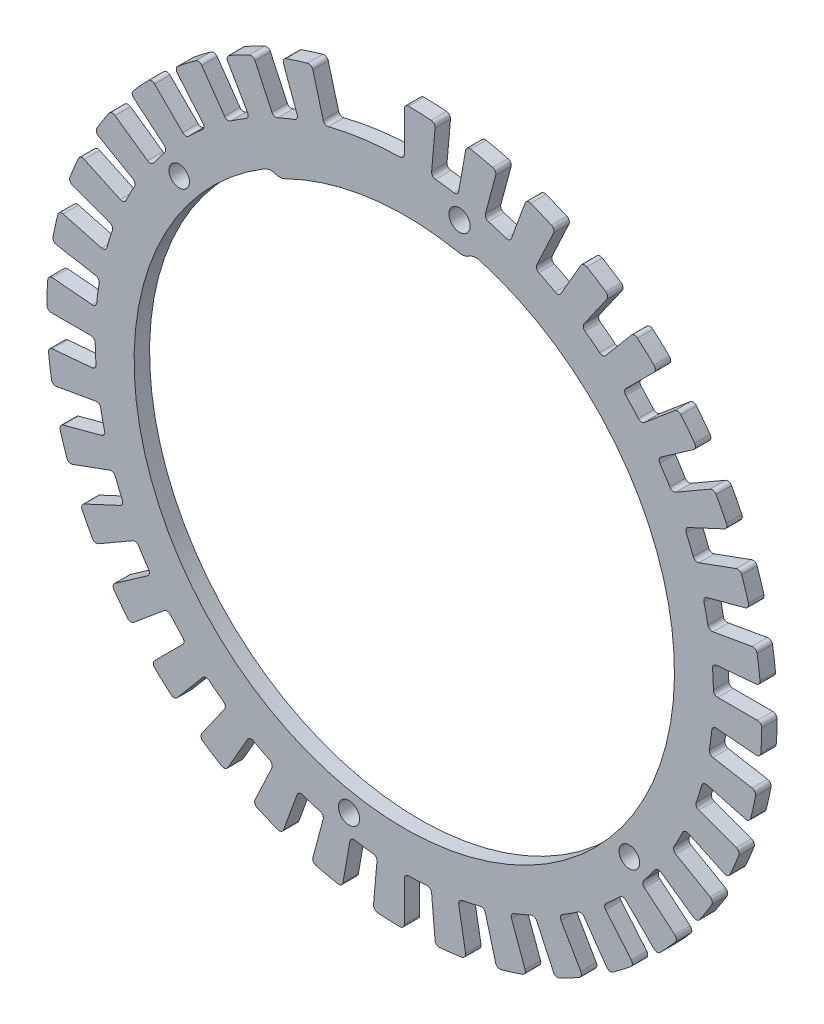
SolidWorks part; units mm, degrees
ref_plane "Front Plane" through (0, 0, 0) normal (0, 0, 1) x (1, 0, 0)
ref_plane "Top Plane" through (0, 0, 0) normal (0, 1, 0) x (1, 0, 0)
ref_plane "Right Plane" through (0, 0, 0) normal (1, 0, 0) x (0, 0, -1)
sketch "Sketch1" plane through (0, 0, 0) normal (0, 0, 1) x (1, 0, 0)
  line L0 (0, 82.7) -> (0, 71.5) construction
  line L1 (7.2078, 82.3853) -> (6.2316, 71.2279) construction
  line L2 (0, 71.5) -> (0, 0) construction
  line L3 (6.2316, 71.2279) -> (0, 0) construction
  line L4 (12.5883, 71.3918) -> (14.186, 80.4528) construction
  line L5 (12.5883, 71.3918) -> (0, 0) construction
  line L8 (0, 0) -> (12.7842, 65.769) construction
  line L12 (13.6428, 70.1863) -> (12.7842, 65.769) construction
  line L15 (12.7842, 65.769) -> (11.9256, 61.3517) construction
  line L18 (7.3144, 72.1301) -> (6.3182, 72.2172) construction
  line L21 (7.3144, 72.1301) -> (7.2135, 71.1352) construction
  line L24 (12.5883, 71.3918) -> (11.6035, 71.5654) construction
  line L27 (11.6035, 71.5654) -> (11.4434, 70.5783) construction
  line L30 (1.0122, 82.6938) -> (1, 81.6939) construction
  line L33 (1, 81.6939) -> (0, 81.6939) construction
  line L36 (7.1201, 81.383) -> (6.1239, 81.4702) construction
  line L39 (6.1239, 81.4702) -> (6.1989, 82.4674) construction
  line L42 (7.1201, 81.383) -> (6.3182, 72.2172)
  line L45 (0, 81.6939) -> (0, 72.4931)
  line L48 (0, 72.4931) -> (-1, 72.4931) construction
  line L51 (-1, 72.4931) -> (-0.9862, 71.4932) construction
  line L109 (0, -82.7) -> (0, -71.5) [skipped]
  line L111 (14.3607, 81.4436) -> (12.4158, 70.4138) [skipped]
  line L115 (41.35, 71.6203) -> (35.75, 61.9208) [skipped]
  line L117 (53.1585, 63.3519) -> (45.9593, 54.7722) [skipped]
  line L118 (-63.3519, -53.1585) -> (-54.7722, -45.9593) [skipped]
  line L119 (63.3519, 53.1585) -> (54.7722, 45.9593) [skipped]
  line L121 (71.6203, 41.35) -> (61.9208, 35.75) [skipped]
  line L123 (77.7126, 28.2851) -> (67.188, 24.4544) [skipped]
  line L125 (81.4436, 14.3607) -> (70.4138, 12.4158) [skipped]
  line L127 (82.7, 0) -> (71.5, 0) [skipped]
  line L129 (81.4436, -14.3607) -> (70.4138, -12.4158) [skipped]
  line L131 (77.7126, -28.2851) -> (67.188, -24.4544) [skipped]
  line L133 (71.6203, -41.35) -> (61.9208, -35.75) [skipped]
  line L135 (63.3519, -53.1585) -> (54.7722, -45.9593) [skipped]
  line L137 (53.1585, -63.3519) -> (45.9593, -54.7722) [skipped]
  line L139 (41.35, -71.6203) -> (35.75, -61.9208) [skipped]
  line L141 (28.2851, -77.7126) -> (24.4544, -67.188) [skipped]
  line L142 (14.3607, -81.4436) -> (12.4158, -70.4138) [skipped]
  line L143 (34.9505, 74.9517) -> (30.2172, 64.801) [skipped]
  line L144 (47.4348, 67.7439) -> (41.0107, 58.5694) [skipped]
  line L145 (58.4777, 58.4777) -> (50.5581, 50.5581) [skipped]
  line L146 (67.7439, 47.4348) -> (58.5694, 41.0107) [skipped]
  line L147 (74.9517, 34.9505) -> (64.801, 30.2172) [skipped]
  line L148 (79.8821, 21.4043) -> (69.0637, 18.5056) [skipped]
  line L149 (82.3853, 7.2078) -> (71.2279, 6.2316) [skipped]
  line L150 (82.3853, -7.2078) -> (71.2279, -6.2316) [skipped]
  line L151 (79.8821, -21.4043) -> (69.0637, -18.5056) [skipped]
  line L152 (74.9517, -34.9505) -> (64.801, -30.2172) [skipped]
  line L153 (67.7439, -47.4348) -> (58.5694, -41.0107) [skipped]
  line L154 (58.4777, -58.4777) -> (50.5581, -50.5581) [skipped]
  line L155 (47.4348, -67.7439) -> (41.0107, -58.5694) [skipped]
  line L156 (34.9505, -74.9517) -> (30.2172, -64.801) [skipped]
  line L157 (21.4043, -79.8821) -> (18.5056, -69.0637) [skipped]
  line L158 (7.2078, -82.3853) -> (6.2316, -71.2279) [skipped]
  line L159 (-7.2078, -82.3853) -> (-6.2316, -71.2279) [skipped]
  line L160 (-21.4043, -79.8821) -> (-18.5056, -69.0637) [skipped]
  line L161 (-34.9505, -74.9517) -> (-30.2172, -64.801) [skipped]
  line L162 (-47.4348, -67.7439) -> (-41.0107, -58.5694) [skipped]
  line L163 (-58.4777, -58.4777) -> (-50.5581, -50.5581) [skipped]
  line L164 (-67.7439, -47.4348) -> (-58.5694, -41.0107) [skipped]
  line L165 (-74.9517, -34.9505) -> (-64.801, -30.2172) [skipped]
  line L166 (-79.8821, -21.4043) -> (-69.0637, -18.5056) [skipped]
  line L167 (-82.3853, -7.2078) -> (-71.2279, -6.2316) [skipped]
  line L168 (-82.3853, 7.2078) -> (-71.2279, 6.2316) [skipped]
  line L169 (-79.8821, 21.4043) -> (-69.0637, 18.5056) [skipped]
  line L170 (-74.9517, 34.9505) -> (-64.801, 30.2172) [skipped]
  line L171 (-67.7439, 47.4348) -> (-58.5694, 41.0107) [skipped]
  line L172 (-58.4777, 58.4777) -> (-50.5581, 50.5581) [skipped]
  line L173 (-47.4348, 67.7439) -> (-41.0107, 58.5694) [skipped]
  line L174 (-34.9505, 74.9517) -> (-30.2172, 64.801) [skipped]
  line L175 (-21.4043, 79.8821) -> (-18.5056, 69.0637) [skipped]
  line L176 (21.4043, 79.8821) -> (18.5056, 69.0637) [skipped]
  line L209 (0, 0) -> (-12.7842, -65.769) construction
  line L210 (0, 0) -> (-52.0688, 42.1645) construction
  line L211 (0, 0) -> (52.0688, -42.1645) construction
  line L212 (14.186, 80.4528) -> (12.5883, 71.3918)
  line L213 (21.1439, 78.9102) -> (18.7626, 70.023)
  line L214 (27.941, 76.7671) -> (24.7941, 68.1212)
  line L215 (34.5253, 74.0398) -> (30.6369, 65.7011)
  line L216 (40.8469, 70.749) -> (36.2466, 62.7809)
  line L217 (46.8577, 66.9197) -> (41.5803, 59.3829)
  line L218 (52.5118, 62.5811) -> (46.5977, 55.5329)
  line L219 (57.7663, 57.7663) -> (51.2604, 51.2604)
  line L220 (62.5811, 52.5118) -> (55.5329, 46.5977)
  line L221 (66.9197, 46.8577) -> (59.3829, 41.5803)
  line L222 (70.749, 40.8469) -> (62.7809, 36.2466)
  line L223 (74.0398, 34.5253) -> (65.7011, 30.6369)
  line L224 (76.7671, 27.941) -> (68.1212, 24.7941)
  line L225 (78.9102, 21.1439) -> (70.023, 18.7626)
  line L226 (80.4528, 14.186) -> (71.3918, 12.5883)
  line L227 (81.383, 7.1201) -> (72.2172, 6.3182)
  line L228 (81.6939, 0) -> (72.4931, 0)
  line L229 (81.383, -7.1201) -> (72.2172, -6.3182)
  line L230 (80.4528, -14.186) -> (71.3918, -12.5883)
  line L231 (78.9102, -21.1439) -> (70.023, -18.7626)
  line L232 (76.7671, -27.941) -> (68.1212, -24.7941)
  line L233 (74.0398, -34.5253) -> (65.7011, -30.6369)
  line L234 (70.749, -40.8469) -> (62.7809, -36.2466)
  line L235 (66.9197, -46.8577) -> (59.3829, -41.5803)
  line L236 (62.5811, -52.5118) -> (55.5329, -46.5977)
  line L237 (57.7663, -57.7663) -> (51.2604, -51.2604)
  line L238 (52.5118, -62.5811) -> (46.5977, -55.5329)
  line L239 (46.8577, -66.9197) -> (41.5803, -59.3829)
  line L240 (40.8469, -70.749) -> (36.2466, -62.7809)
  line L241 (34.5253, -74.0398) -> (30.6369, -65.7011)
  line L242 (27.941, -76.7671) -> (24.7941, -68.1212)
  line L243 (21.1439, -78.9102) -> (18.7626, -70.023)
  line L244 (14.186, -80.4528) -> (12.5883, -71.3918)
  line L245 (7.1201, -81.383) -> (6.3182, -72.2172)
  line L246 (0, -81.6939) -> (0, -72.4931)
  line L247 (-7.1201, -81.383) -> (-6.3182, -72.2172)
  line L248 (-14.186, -80.4528) -> (-12.5883, -71.3918)
  line L249 (-21.1439, -78.9102) -> (-18.7626, -70.023)
  line L250 (-27.941, -76.7671) -> (-24.7941, -68.1212)
  line L251 (-34.5253, -74.0398) -> (-30.6369, -65.7011)
  line L252 (-40.8469, -70.749) -> (-36.2466, -62.7809)
  line L253 (-46.8577, -66.9197) -> (-41.5803, -59.3829)
  line L254 (-52.5118, -62.5811) -> (-46.5977, -55.5329)
  line L255 (-57.7663, -57.7663) -> (-51.2604, -51.2604)
  line L256 (-62.5811, -52.5118) -> (-55.5329, -46.5977)
  line L257 (-66.9197, -46.8577) -> (-59.3829, -41.5803)
  line L258 (-70.749, -40.8469) -> (-62.7809, -36.2466)
  line L259 (-74.0398, -34.5253) -> (-65.7011, -30.6369)
  line L260 (-76.7671, -27.941) -> (-68.1212, -24.7941)
  line L261 (-78.9102, -21.1439) -> (-70.023, -18.7626)
  line L262 (-80.4528, -14.186) -> (-71.3918, -12.5883)
  line L263 (-81.383, -7.1201) -> (-72.2172, -6.3182)
  line L264 (-81.6939, 0) -> (-72.4931, 0)
  line L265 (-81.383, 7.1201) -> (-72.2172, 6.3182)
  line L266 (-80.4528, 14.186) -> (-71.3918, 12.5883)
  line L267 (-78.9102, 21.1439) -> (-70.023, 18.7626)
  line L268 (-76.7671, 27.941) -> (-68.1212, 24.7941)
  line L269 (-74.0398, 34.5253) -> (-65.7011, 30.6369)
  line L270 (-70.749, 40.8469) -> (-62.7809, 36.2466)
  line L271 (-66.9197, 46.8577) -> (-59.3829, 41.5803)
  line L272 (-62.5811, 52.5118) -> (-55.5329, 46.5977)
  line L273 (-57.7663, 57.7663) -> (-51.2604, 51.2604)
  line L274 (-52.5118, 62.5811) -> (-46.5977, 55.5329)
  line L275 (-46.8577, 66.9197) -> (-41.5803, 59.3829)
  line L276 (-40.8469, 70.749) -> (-36.2466, 62.7809)
  line L277 (-34.5253, 74.0398) -> (-30.6369, 65.7011)
  line L278 (-27.941, 76.7671) -> (-24.7941, 68.1212)
  line L279 (-21.1439, 78.9102) -> (-18.7626, 70.023)
  line L280 (-0.9864, 71.4932) -> (-0.9862, 71.4932)
  line L281 (-32.3995, 53.4464) -> (-30.8444, 50.881) construction
  line L282 (-30.8444, 50.881) -> (-29.8635, 53.7161) construction
  line L283 (-29.8635, 53.7161) -> (-28.8826, 56.5512) construction
  line L284 (-28.8826, 56.5512) -> (-27.5181, 53.8795) construction
  line L285 (17.4626, 60.0109) -> (16.6244, 57.1304) construction
  line L286 (16.6244, 57.1304) -> (14.9432, 59.615) construction
  line L289 (13.262, 62.0997) -> (14.9432, 59.615) construction
  line L290 (-7.4414, 56.5227) -> (0, 0) construction
  line L291 (-27.5181, 53.8795) -> (-7.4414, 56.5227) construction
  line L292 (-7.4414, 56.5227) -> (12.6354, 59.1658) construction
  line L293 (13.262, 62.0997) -> (12.6354, 59.1658) construction
  line L294 (-28.4278, 55.6607) -> (13.0531, 61.1217) construction
  circle A0 centre (0, 0) radius 82.7 construction
  arc A1 (-32.3995, 53.4464) -> (17.4626, 60.0109) centre (0, 0) ccw
  circle A73 centre (12.7842, 65.769) radius 2.4585
  circle A74 centre (12.7842, 65.769) radius 2.987 construction
  arc A78 (0, 71.5) -> (6.2316, 71.2279) centre (0, 0) cw construction
  arc A79 (6.3182, 72.2172) -> (7.2135, 71.1352) centre (7.3144, 72.1301) ccw
  arc A80 (11.4434, 70.5783) -> (12.5883, 71.3918) centre (11.6035, 71.5654) ccw construction
  arc A81 (7.1201, 81.383) -> (6.1989, 82.4674) centre (6.1239, 81.4702) ccw
  arc A82 (0, 81.6939) -> (1.0122, 82.6938) centre (1, 81.6939) cw
  arc A83 (6.5367, 74.7146) -> (13.0236, 73.8606) centre (0, 0) cw [skipped]
  arc A84 (7.2135, 71.1352) -> (11.4434, 70.5783) centre (0, 0) cw
  arc A85 (0, 82.7) -> (7.2078, 82.3853) centre (0, 0) cw [skipped]
  arc A86 (1.0122, 82.6938) -> (6.1989, 82.4674) centre (0, 0) cw
  arc A87 (28.2851, 77.7126) -> (34.9505, 74.9517) centre (0, 0) cw [skipped]
  arc A88 (31.6964, 67.9731) -> (37.5, 64.9519) centre (0, 0) cw [skipped]
  arc A89 (41.35, 71.6203) -> (47.4348, 67.7439) centre (0, 0) cw [skipped]
  arc A90 (43.0182, 61.4364) -> (48.2091, 57.4533) centre (0, 0) cw [skipped]
  arc A91 (53.1585, 63.3519) -> (58.4777, 58.4777) centre (0, 0) cw [skipped]
  arc A92 (53.033, 53.033) -> (57.4533, 48.2091) centre (0, 0) cw [skipped]
  arc A93 (63.3519, 53.1585) -> (67.7439, 47.4348) centre (0, 0) cw [skipped]
  arc A94 (61.4364, 43.0182) -> (64.9519, 37.5) centre (0, 0) cw [skipped]
  arc A95 (71.6203, 41.35) -> (74.9517, 34.9505) centre (0, 0) cw [skipped]
  arc A96 (67.9731, 31.6964) -> (70.4769, 25.6515) centre (0, 0) cw [skipped]
  arc A97 (77.7126, 28.2851) -> (79.8821, 21.4043) centre (0, 0) cw [skipped]
  arc A98 (72.4444, 19.4114) -> (73.8606, 13.0236) centre (0, 0) cw [skipped]
  arc A99 (81.4436, 14.3607) -> (82.3853, 7.2078) centre (0, 0) cw [skipped]
  arc A100 (74.7146, 6.5367) -> (75, 0) centre (0, 0) cw [skipped]
  arc A101 (82.7, 0) -> (82.3853, -7.2078) centre (0, 0) cw [skipped]
  arc A102 (74.7146, -6.5367) -> (73.8606, -13.0236) centre (0, 0) cw [skipped]
  arc A103 (81.4436, -14.3607) -> (79.8821, -21.4043) centre (0, 0) cw [skipped]
  arc A104 (72.4444, -19.4114) -> (70.4769, -25.6515) centre (0, 0) cw [skipped]
  arc A105 (77.7126, -28.2851) -> (74.9517, -34.9505) centre (0, 0) cw [skipped]
  arc A106 (67.9731, -31.6964) -> (64.9519, -37.5) centre (0, 0) cw [skipped]
  arc A107 (71.6203, -41.35) -> (67.7439, -47.4348) centre (0, 0) cw [skipped]
  arc A108 (61.4364, -43.0182) -> (57.4533, -48.2091) centre (0, 0) cw [skipped]
  arc A109 (63.3519, -53.1585) -> (58.4777, -58.4777) centre (0, 0) cw [skipped]
  arc A110 (53.033, -53.033) -> (48.2091, -57.4533) centre (0, 0) cw [skipped]
  arc A111 (53.1585, -63.3519) -> (47.4348, -67.7439) centre (0, 0) cw [skipped]
  arc A112 (43.0182, -61.4364) -> (37.5, -64.9519) centre (0, 0) cw [skipped]
  arc A113 (41.35, -71.6203) -> (34.9505, -74.9517) centre (0, 0) cw [skipped]
  arc A114 (31.6964, -67.9731) -> (25.6515, -70.4769) centre (0, 0) cw [skipped]
  arc A115 (28.2851, -77.7126) -> (21.4043, -79.8821) centre (0, 0) cw [skipped]
  arc A116 (19.4114, -72.4444) -> (13.0236, -73.8606) centre (0, 0) cw [skipped]
  arc A117 (14.3607, -81.4436) -> (7.2078, -82.3853) centre (0, 0) cw [skipped]
  arc A118 (6.5367, -74.7146) -> (0, -75) centre (0, 0) cw [skipped]
  arc A119 (0, -82.7) -> (-7.2078, -82.3853) centre (0, 0) cw [skipped]
  arc A120 (-6.5367, -74.7146) -> (-13.0236, -73.8606) centre (0, 0) cw [skipped]
  arc A121 (-14.3607, -81.4436) -> (-21.4043, -79.8821) centre (0, 0) cw [skipped]
  arc A122 (-28.2851, -77.7126) -> (-34.9505, -74.9517) centre (0, 0) cw [skipped]
  arc A123 (-19.4114, -72.4444) -> (-25.6515, -70.4769) centre (0, 0) cw [skipped]
  arc A124 (-31.6964, -67.9731) -> (-37.5, -64.9519) centre (0, 0) cw [skipped]
  arc A125 (-41.35, -71.6203) -> (-47.4348, -67.7439) centre (0, 0) cw [skipped]
  arc A126 (-43.0182, -61.4364) -> (-48.2091, -57.4533) centre (0, 0) cw [skipped]
  arc A127 (-53.1585, -63.3519) -> (-58.4777, -58.4777) centre (0, 0) cw [skipped]
  arc A128 (-53.033, -53.033) -> (-57.4533, -48.2091) centre (0, 0) cw [skipped]
  arc A129 (-63.3519, -53.1585) -> (-67.7439, -47.4348) centre (0, 0) cw [skipped]
  arc A130 (-61.4364, -43.0182) -> (-64.9519, -37.5) centre (0, 0) cw [skipped]
  arc A131 (-71.6203, -41.35) -> (-74.9517, -34.9505) centre (0, 0) cw [skipped]
  arc A132 (-67.9731, -31.6964) -> (-70.4769, -25.6515) centre (0, 0) cw [skipped]
  arc A133 (-77.7126, -28.2851) -> (-79.8821, -21.4043) centre (0, 0) cw [skipped]
  arc A134 (-72.4444, -19.4114) -> (-73.8606, -13.0236) centre (0, 0) cw [skipped]
  arc A135 (-81.4436, -14.3607) -> (-82.3853, -7.2078) centre (0, 0) cw [skipped]
  arc A136 (-74.7146, -6.5367) -> (-75, 0) centre (0, 0) cw [skipped]
  arc A137 (-82.7, 0) -> (-82.3853, 7.2078) centre (0, 0) cw [skipped]
  arc A138 (-74.7146, 6.5367) -> (-73.8606, 13.0236) centre (0, 0) cw [skipped]
  arc A139 (-81.4436, 14.3607) -> (-79.8821, 21.4043) centre (0, 0) cw [skipped]
  arc A140 (-72.4444, 19.4114) -> (-70.4769, 25.6515) centre (0, 0) cw [skipped]
  arc A141 (-77.7126, 28.2851) -> (-74.9517, 34.9505) centre (0, 0) cw [skipped]
  arc A142 (-67.9731, 31.6964) -> (-64.9519, 37.5) centre (0, 0) cw [skipped]
  arc A143 (-71.6203, 41.35) -> (-67.7439, 47.4348) centre (0, 0) cw [skipped]
  arc A144 (-61.4364, 43.0182) -> (-57.4533, 48.2091) centre (0, 0) cw [skipped]
  arc A145 (-63.3519, 53.1585) -> (-58.4777, 58.4777) centre (0, 0) cw [skipped]
  arc A146 (-53.033, 53.033) -> (-48.2091, 57.4533) centre (0, 0) cw [skipped]
  arc A147 (-53.1585, 63.3519) -> (-47.4348, 67.7439) centre (0, 0) cw [skipped]
  arc A148 (-43.0182, 61.4364) -> (-37.5, 64.9519) centre (0, 0) cw [skipped]
  arc A149 (-41.35, 71.6203) -> (-34.9505, 74.9517) centre (0, 0) cw [skipped]
  arc A150 (-31.6964, 67.9731) -> (-25.6515, 70.4769) centre (0, 0) cw [skipped]
  arc A151 (-28.2851, 77.7126) -> (-21.4043, 79.8821) centre (0, 0) cw [skipped]
  arc A152 (-19.4114, 72.4444) -> (-13.0236, 73.8606) centre (0, 0) cw [skipped]
  arc A153 (14.3607, 81.4436) -> (21.4043, 79.8821) centre (0, 0) cw [skipped]
  arc A154 (19.4114, 72.4444) -> (25.6515, 70.4769) centre (0, 0) cw [skipped]
  arc A155 (0, 72.4931) -> (-0.9862, 71.4932) centre (-1, 72.4931) cw
  circle A367 centre (-12.7842, -65.769) radius 2.4585
  circle A368 centre (52.0688, -42.1645) radius 2.3812
  circle A369 centre (-52.0688, 42.1645) radius 2.3813
  circle A370 centre (0, 0) radius 71.5 construction
  arc A371 (12.5883, 71.3918) -> (11.4434, 70.5783) centre (11.6035, 71.5654) cw
  arc A372 (14.186, 80.4528) -> (15.3565, 81.2617) centre (15.1708, 80.2791) cw
  arc A373 (15.3565, 81.2617) -> (20.425, 80.1381) centre (0, 0) cw
  arc A374 (21.1439, 78.9102) -> (20.425, 80.1381) centre (20.178, 79.169) ccw
  arc A375 (18.7626, 70.023) -> (19.4564, 68.8019) centre (19.7285, 69.7641) ccw
  arc A376 (19.4564, 68.8019) -> (23.5254, 67.5189) centre (0, 0) cw
  arc A377 (24.7941, 68.1212) -> (23.5254, 67.5189) centre (23.8544, 68.4633) cw
  arc A378 (27.941, 76.7671) -> (29.2341, 77.3606) centre (28.8806, 76.4251) cw
  arc A379 (29.2341, 77.3606) -> (34.0305, 75.3738) centre (0, 0) cw
  arc A380 (34.5253, 74.0398) -> (34.0305, 75.3738) centre (33.619, 74.4624) ccw
  arc A381 (30.6369, 65.7011) -> (31.1081, 64.3781) centre (31.5432, 65.2784) ccw
  arc A382 (31.1081, 64.3781) -> (34.8925, 62.408) centre (0, 0) cw
  arc A384 (36.2466, 62.7809) -> (34.8925, 62.408) centre (35.3805, 63.2809) cw
  arc A385 (40.8469, 70.749) -> (42.2235, 71.1088) centre (41.713, 70.249) cw
  arc A386 (42.2235, 71.1088) -> (46.602, 68.3194) centre (0, 0) cw
  arc A387 (46.8577, 66.9197) -> (46.602, 68.3194) centre (46.0385, 67.4933) ccw
  arc A388 (41.5803, 59.3829) -> (41.8147, 57.9981) centre (42.3995, 58.8093) ccw
  arc A389 (41.8147, 57.9981) -> (45.1995, 55.4009) centre (0, 0) cw
  arc A390 (46.5977, 55.5329) -> (45.1995, 55.4009) centre (45.8316, 56.1757) cw
  arc A391 (52.5118, 62.5811) -> (53.93, 62.6965) centre (53.2779, 61.9384) cw
  arc A392 (53.93, 62.6965) -> (57.7576, 59.1891) centre (0, 0) cw
  arc A393 (57.7663, 57.7663) -> (57.7576, 59.1891) centre (57.0592, 58.4734) ccw
  arc A394 (51.2604, 51.2604) -> (51.2507, 49.856) centre (51.9675, 50.5533) ccw
  arc A395 (51.2507, 49.856) -> (54.133, 46.7104) centre (0, 0) cw
  arc A396 (55.5329, 46.5977) -> (54.133, 46.7104) centre (54.8902, 47.3637) cw
  arc A397 (62.5811, 52.5118) -> (63.9978, 52.3791) centre (63.2239, 51.7458) cw
  arc A398 (63.9978, 52.3791) -> (67.1582, 48.2604) centre (0, 0) cw
  arc A399 (66.9197, 46.8577) -> (67.1582, 48.2604) centre (66.3461, 47.6768) ccw
  arc A400 (59.3829, 41.5803) -> (59.1295, 40.199) centre (59.9565, 40.7612) ccw
  arc A401 (59.1295, 40.199) -> (61.4218, 36.6007) centre (0, 0) cw
  arc A402 (62.7809, 36.2466) -> (61.4218, 36.6007) centre (62.2809, 37.1126) cw
  arc A403 (70.749, 40.8469) -> (72.1211, 40.4703) centre (71.249, 39.9809) cw
  arc A404 (72.1211, 40.4703) -> (74.5182, 35.8653) centre (0, 0) cw
  arc A405 (74.0398, 34.5253) -> (74.5182, 35.8653) centre (73.6172, 35.4316) ccw
  arc A406 (65.7011, 30.6369) -> (65.2116, 29.3205) centre (66.1237, 29.7306) ccw
  arc A407 (65.2116, 29.3205) -> (66.8443, 25.3788) centre (0, 0) cw
  arc A408 (68.1212, 24.7941) -> (66.8443, 25.3788) centre (67.7792, 25.7338) cw
  arc A409 (76.7671, 27.941) -> (78.053, 27.3318) centre (77.1092, 27.0013) cw
  arc A410 (78.053, 27.3318) -> (79.6141, 22.3805) centre (0, 0) cw
  arc A411 (78.9102, 21.1439) -> (79.6141, 22.3805) centre (78.6514, 22.1099) ccw
  arc A412 (70.023, 18.7626) -> (69.3124, 17.5512) centre (70.2818, 17.7967) ccw
  arc A413 (69.3124, 17.5512) -> (70.2358, 13.3859) centre (0, 0) cw
  arc A414 (71.3918, 12.5883) -> (70.2358, 13.3859) centre (71.2181, 13.5731) cw
  arc A415 (80.4528, 14.186) -> (81.6133, 13.3628) centre (80.6264, 13.2012) cw
  arc A416 (81.6133, 13.3628) -> (82.2909, 8.2156) centre (0, 0) cw
  arc A417 (81.383, 7.1201) -> (82.2909, 8.2156) centre (81.2959, 8.1163) ccw
  arc A418 (72.2172, 6.3182) -> (71.3071, 5.2486) centre (72.3044, 5.322) ccw
  arc A419 (71.3071, 5.2486) -> (71.4932, 0.9862) centre (0, 0) cw
  arc A420 (72.4931, 0) -> (71.4932, 0.9862) centre (72.4931, 1) cw
  arc A421 (81.6939, 0) -> (82.6938, -1.0122) centre (81.6939, -1) cw
  arc A422 (82.6938, -1.0122) -> (82.4674, -6.1989) centre (0, 0) cw
  arc A423 (81.383, -7.1201) -> (82.4674, -6.1989) centre (81.4702, -6.1239) ccw
  arc A424 (72.2172, -6.3182) -> (71.1352, -7.2135) centre (72.1301, -7.3144) ccw
  arc A425 (71.1352, -7.2135) -> (70.5783, -11.4434) centre (0, 0) cw
  arc A426 (71.3918, -12.5883) -> (70.5783, -11.4434) centre (71.5654, -11.6035) cw
  arc A427 (80.4528, -14.186) -> (81.2617, -15.3565) centre (80.2791, -15.1708) cw
  arc A428 (81.2617, -15.3565) -> (80.1381, -20.425) centre (0, 0) cw
  arc A429 (78.9102, -21.1439) -> (80.1381, -20.425) centre (79.169, -20.178) ccw
  arc A430 (70.023, -18.7626) -> (68.8019, -19.4564) centre (69.7641, -19.7285) ccw
  arc A431 (68.8019, -19.4564) -> (67.5189, -23.5254) centre (0, 0) cw
  arc A432 (68.1212, -24.7941) -> (67.5189, -23.5254) centre (68.4633, -23.8544) cw
  arc A433 (76.7671, -27.941) -> (77.3606, -29.2341) centre (76.4251, -28.8806) cw
  arc A434 (77.3606, -29.2341) -> (75.3738, -34.0305) centre (0, 0) cw
  arc A435 (74.0398, -34.5253) -> (75.3738, -34.0305) centre (74.4624, -33.619) ccw
  arc A436 (65.7011, -30.6369) -> (64.3781, -31.1081) centre (65.2784, -31.5432) ccw
  arc A437 (64.3781, -31.1081) -> (62.408, -34.8925) centre (0, 0) cw
  arc A438 (62.7809, -36.2466) -> (62.408, -34.8925) centre (63.2809, -35.3805) cw
  arc A439 (70.749, -40.8469) -> (71.1088, -42.2235) centre (70.249, -41.713) cw
  arc A440 (71.1088, -42.2235) -> (68.3194, -46.602) centre (0, 0) cw
  arc A441 (66.9197, -46.8577) -> (68.3194, -46.602) centre (67.4933, -46.0385) ccw
  arc A442 (59.3829, -41.5803) -> (57.9981, -41.8147) centre (58.8093, -42.3995) ccw
  arc A443 (57.9981, -41.8147) -> (55.4009, -45.1995) centre (0, 0) cw
  arc A444 (55.5329, -46.5977) -> (55.4009, -45.1995) centre (56.1757, -45.8316) cw
  arc A445 (62.5811, -52.5118) -> (62.6965, -53.93) centre (61.9384, -53.2779) cw
  arc A446 (62.6965, -53.93) -> (59.1891, -57.7576) centre (0, 0) cw
  arc A447 (57.7663, -57.7663) -> (59.1891, -57.7576) centre (58.4734, -57.0592) ccw
  arc A448 (51.2604, -51.2604) -> (49.856, -51.2507) centre (50.5533, -51.9675) ccw
  arc A449 (49.856, -51.2507) -> (46.7104, -54.133) centre (0, 0) cw
  arc A450 (46.5977, -55.5329) -> (46.7104, -54.133) centre (47.3637, -54.8902) cw
  arc A451 (52.5118, -62.5811) -> (52.3791, -63.9978) centre (51.7458, -63.2239) cw
  arc A452 (52.3791, -63.9978) -> (48.2604, -67.1582) centre (0, 0) cw
  arc A453 (46.8577, -66.9197) -> (48.2604, -67.1582) centre (47.6768, -66.3461) ccw
  arc A454 (41.5803, -59.3829) -> (40.199, -59.1295) centre (40.7612, -59.9565) ccw
  arc A455 (40.199, -59.1295) -> (36.6007, -61.4218) centre (0, 0) cw
  arc A456 (36.2466, -62.7809) -> (36.6007, -61.4218) centre (37.1126, -62.2809) cw
  arc A457 (40.8469, -70.749) -> (40.4703, -72.1211) centre (39.9809, -71.249) cw
  arc A458 (40.4703, -72.1211) -> (35.8653, -74.5182) centre (0, 0) cw
  arc A459 (34.5253, -74.0398) -> (35.8653, -74.5182) centre (35.4316, -73.6172) ccw
  arc A460 (30.6369, -65.7011) -> (29.3205, -65.2116) centre (29.7306, -66.1237) ccw
  arc A461 (29.3205, -65.2116) -> (25.3788, -66.8443) centre (0, 0) cw
  arc A462 (24.7941, -68.1212) -> (25.3788, -66.8443) centre (25.7338, -67.7792) cw
  arc A463 (27.941, -76.7671) -> (27.3318, -78.053) centre (27.0013, -77.1092) cw
  arc A464 (27.3318, -78.053) -> (22.3805, -79.6141) centre (0, 0) cw
  arc A465 (21.1439, -78.9102) -> (22.3805, -79.6141) centre (22.1099, -78.6514) ccw
  arc A466 (18.7626, -70.023) -> (17.5512, -69.3124) centre (17.7967, -70.2818) ccw
  arc A467 (17.5512, -69.3124) -> (13.3859, -70.2358) centre (0, 0) cw
  arc A468 (12.5883, -71.3918) -> (13.3859, -70.2358) centre (13.5731, -71.2181) cw
  arc A469 (14.186, -80.4528) -> (13.3628, -81.6133) centre (13.2012, -80.6264) cw
  arc A470 (13.3628, -81.6133) -> (8.2156, -82.2909) centre (0, 0) cw
  arc A471 (7.1201, -81.383) -> (8.2156, -82.2909) centre (8.1163, -81.2959) ccw
  arc A472 (6.3182, -72.2172) -> (5.2486, -71.3071) centre (5.322, -72.3044) ccw
  arc A473 (5.2486, -71.3071) -> (0.9862, -71.4932) centre (0, 0) cw
  arc A474 (0, -72.4931) -> (0.9862, -71.4932) centre (1, -72.4931) cw
  arc A475 (0, -81.6939) -> (-1.0122, -82.6938) centre (-1, -81.6939) cw
  arc A476 (-1.0122, -82.6938) -> (-6.1989, -82.4674) centre (0, 0) cw
  arc A477 (-7.1201, -81.383) -> (-6.1989, -82.4674) centre (-6.1239, -81.4702) ccw
  arc A478 (-6.3182, -72.2172) -> (-7.2135, -71.1352) centre (-7.3144, -72.1301) ccw
  arc A479 (-7.2135, -71.1352) -> (-11.4434, -70.5783) centre (0, 0) cw
  arc A480 (-12.5883, -71.3918) -> (-11.4434, -70.5783) centre (-11.6035, -71.5654) cw
  arc A481 (-14.186, -80.4528) -> (-15.3565, -81.2617) centre (-15.1708, -80.2791) cw
  arc A482 (-15.3565, -81.2617) -> (-20.425, -80.1381) centre (0, 0) cw
  arc A483 (-21.1439, -78.9102) -> (-20.425, -80.1381) centre (-20.178, -79.169) ccw
  arc A484 (-18.7626, -70.023) -> (-19.4564, -68.8019) centre (-19.7285, -69.7641) ccw
  arc A485 (-19.4564, -68.8019) -> (-23.5254, -67.5189) centre (0, 0) cw
  arc A486 (-24.7941, -68.1212) -> (-23.5254, -67.5189) centre (-23.8544, -68.4633) cw
  arc A487 (-27.941, -76.7671) -> (-29.2341, -77.3606) centre (-28.8806, -76.4251) cw
  arc A488 (-29.2341, -77.3606) -> (-34.0305, -75.3738) centre (0, 0) cw
  arc A489 (-34.5253, -74.0398) -> (-34.0305, -75.3738) centre (-33.619, -74.4624) ccw
  arc A490 (-30.6369, -65.7011) -> (-31.1081, -64.3781) centre (-31.5432, -65.2784) ccw
  arc A491 (-31.1081, -64.3781) -> (-34.8925, -62.408) centre (0, 0) cw
  arc A492 (-36.2466, -62.7809) -> (-34.8925, -62.408) centre (-35.3805, -63.2809) cw
  arc A493 (-40.8469, -70.749) -> (-42.2235, -71.1088) centre (-41.713, -70.249) cw
  arc A494 (-42.2235, -71.1088) -> (-46.602, -68.3194) centre (0, 0) cw
  arc A495 (-46.8577, -66.9197) -> (-46.602, -68.3194) centre (-46.0385, -67.4933) ccw
  arc A496 (-41.5803, -59.3829) -> (-41.8147, -57.9981) centre (-42.3995, -58.8093) ccw
  arc A497 (-41.8147, -57.9981) -> (-45.1995, -55.4009) centre (0, 0) cw
  arc A498 (-46.5977, -55.5329) -> (-45.1995, -55.4009) centre (-45.8316, -56.1757) cw
  arc A499 (-52.5118, -62.5811) -> (-53.93, -62.6965) centre (-53.2779, -61.9384) cw
  arc A500 (-53.93, -62.6965) -> (-57.7576, -59.1891) centre (0, 0) cw
  arc A501 (-57.7663, -57.7663) -> (-57.7576, -59.1891) centre (-57.0592, -58.4734) ccw
  arc A502 (-51.2604, -51.2604) -> (-51.2507, -49.856) centre (-51.9675, -50.5533) ccw
  arc A503 (-51.2507, -49.856) -> (-54.133, -46.7104) centre (0, 0) cw
  arc A504 (-55.5329, -46.5977) -> (-54.133, -46.7104) centre (-54.8902, -47.3637) cw
  arc A505 (-62.5811, -52.5118) -> (-63.9978, -52.3791) centre (-63.2239, -51.7458) cw
  arc A506 (-63.9978, -52.3791) -> (-67.1582, -48.2604) centre (0, 0) cw
  arc A507 (-66.9197, -46.8577) -> (-67.1582, -48.2604) centre (-66.3461, -47.6768) ccw
  arc A508 (-59.3829, -41.5803) -> (-59.1295, -40.199) centre (-59.9565, -40.7612) ccw
  arc A509 (-59.1295, -40.199) -> (-61.4218, -36.6007) centre (0, 0) cw
  arc A510 (-62.7809, -36.2466) -> (-61.4218, -36.6007) centre (-62.2809, -37.1126) cw
  arc A511 (-70.749, -40.8469) -> (-72.1211, -40.4703) centre (-71.249, -39.9809) cw
  arc A512 (-72.1211, -40.4703) -> (-74.5182, -35.8653) centre (0, 0) cw
  arc A513 (-74.0398, -34.5253) -> (-74.5182, -35.8653) centre (-73.6172, -35.4316) ccw
  arc A514 (-65.7011, -30.6369) -> (-65.2116, -29.3205) centre (-66.1237, -29.7306) ccw
  arc A515 (-65.2116, -29.3205) -> (-66.8443, -25.3788) centre (0, 0) cw
  arc A516 (-68.1212, -24.7941) -> (-66.8443, -25.3788) centre (-67.7792, -25.7338) cw
  arc A517 (-76.7671, -27.941) -> (-78.053, -27.3318) centre (-77.1092, -27.0013) cw
  arc A518 (-78.053, -27.3318) -> (-79.6141, -22.3805) centre (0, 0) cw
  arc A519 (-78.9102, -21.1439) -> (-79.6141, -22.3805) centre (-78.6514, -22.1099) ccw
  arc A520 (-70.023, -18.7626) -> (-69.3124, -17.5512) centre (-70.2818, -17.7967) ccw
  arc A521 (-69.3124, -17.5512) -> (-70.2358, -13.3859) centre (0, 0) cw
  arc A522 (-71.3918, -12.5883) -> (-70.2358, -13.3859) centre (-71.2181, -13.5731) cw
  arc A523 (-80.4528, -14.186) -> (-81.6133, -13.3628) centre (-80.6264, -13.2012) cw
  arc A524 (-81.6133, -13.3628) -> (-82.2909, -8.2156) centre (0, 0) cw
  arc A525 (-81.383, -7.1201) -> (-82.2909, -8.2156) centre (-81.2959, -8.1163) ccw
  arc A526 (-72.2172, -6.3182) -> (-71.3071, -5.2486) centre (-72.3044, -5.322) ccw
  arc A527 (-71.3071, -5.2486) -> (-71.4932, -0.9862) centre (0, 0) cw
  arc A528 (-72.4931, 0) -> (-71.4932, -0.9862) centre (-72.4931, -1) cw
  arc A529 (-81.6939, 0) -> (-82.6938, 1.0122) centre (-81.6939, 1) cw
  arc A530 (-82.6938, 1.0122) -> (-82.4674, 6.1989) centre (0, 0) cw
  arc A531 (-81.383, 7.1201) -> (-82.4674, 6.1989) centre (-81.4702, 6.1239) ccw
  arc A532 (-72.2172, 6.3182) -> (-71.1352, 7.2135) centre (-72.1301, 7.3144) ccw
  arc A533 (-71.1352, 7.2135) -> (-70.5783, 11.4434) centre (0, 0) cw
  arc A534 (-71.3918, 12.5883) -> (-70.5783, 11.4434) centre (-71.5654, 11.6035) cw
  arc A535 (-80.4528, 14.186) -> (-81.2617, 15.3565) centre (-80.2791, 15.1708) cw
  arc A536 (-81.2617, 15.3565) -> (-80.1381, 20.425) centre (0, 0) cw
  arc A537 (-78.9102, 21.1439) -> (-80.1381, 20.425) centre (-79.169, 20.178) ccw
  arc A538 (-70.023, 18.7626) -> (-68.8019, 19.4564) centre (-69.7641, 19.7285) ccw
  arc A539 (-68.8019, 19.4564) -> (-67.5189, 23.5254) centre (0, 0) cw
  arc A540 (-68.1212, 24.7941) -> (-67.5189, 23.5254) centre (-68.4633, 23.8544) cw
  arc A541 (-76.7671, 27.941) -> (-77.3606, 29.2341) centre (-76.4251, 28.8806) cw
  arc A542 (-77.3606, 29.2341) -> (-75.3738, 34.0305) centre (0, 0) cw
  arc A543 (-74.0398, 34.5253) -> (-75.3738, 34.0305) centre (-74.4624, 33.619) ccw
  arc A544 (-65.7011, 30.6369) -> (-64.3781, 31.1081) centre (-65.2784, 31.5432) ccw
  arc A545 (-64.3781, 31.1081) -> (-62.408, 34.8925) centre (0, 0) cw
  arc A546 (-62.7809, 36.2466) -> (-62.408, 34.8925) centre (-63.2809, 35.3805) cw
  arc A547 (-70.749, 40.8469) -> (-71.1088, 42.2235) centre (-70.249, 41.713) cw
  arc A548 (-71.1088, 42.2235) -> (-68.3194, 46.602) centre (0, 0) cw
  arc A549 (-66.9197, 46.8577) -> (-68.3194, 46.602) centre (-67.4933, 46.0385) ccw
  arc A550 (-59.3829, 41.5803) -> (-57.9981, 41.8147) centre (-58.8093, 42.3995) ccw
  arc A551 (-57.9981, 41.8147) -> (-55.4009, 45.1995) centre (0, 0) cw
  arc A552 (-55.5329, 46.5977) -> (-55.4009, 45.1995) centre (-56.1757, 45.8316) cw
  arc A553 (-62.5811, 52.5118) -> (-62.6965, 53.93) centre (-61.9384, 53.2779) cw
  arc A554 (-62.6965, 53.93) -> (-59.1891, 57.7576) centre (0, 0) cw
  arc A555 (-57.7663, 57.7663) -> (-59.1891, 57.7576) centre (-58.4734, 57.0592) ccw
  arc A556 (-51.2604, 51.2604) -> (-49.856, 51.2507) centre (-50.5533, 51.9675) ccw
  arc A557 (-49.856, 51.2507) -> (-46.7104, 54.133) centre (0, 0) cw
  arc A558 (-46.5977, 55.5329) -> (-46.7104, 54.133) centre (-47.3637, 54.8902) cw
  arc A559 (-52.5118, 62.5811) -> (-52.3791, 63.9978) centre (-51.7458, 63.2239) cw
  arc A560 (-52.3791, 63.9978) -> (-48.2604, 67.1582) centre (0, 0) cw
  arc A561 (-46.8577, 66.9197) -> (-48.2604, 67.1582) centre (-47.6768, 66.3461) ccw
  arc A562 (-41.5803, 59.3829) -> (-40.199, 59.1295) centre (-40.7612, 59.9565) ccw
  arc A563 (-40.199, 59.1295) -> (-36.6007, 61.4218) centre (0, 0) cw
  arc A564 (-36.2466, 62.7809) -> (-36.6007, 61.4218) centre (-37.1126, 62.2809) cw
  arc A565 (-40.8469, 70.749) -> (-40.4703, 72.1211) centre (-39.9809, 71.249) cw
  arc A566 (-40.4703, 72.1211) -> (-35.8653, 74.5182) centre (0, 0) cw
  arc A567 (-34.5253, 74.0398) -> (-35.8653, 74.5182) centre (-35.4316, 73.6172) ccw
  arc A568 (-30.6369, 65.7011) -> (-29.3205, 65.2116) centre (-29.7306, 66.1237) ccw
  arc A569 (-29.3205, 65.2116) -> (-25.3788, 66.8443) centre (0, 0) cw
  arc A570 (-24.7941, 68.1212) -> (-25.3788, 66.8443) centre (-25.7338, 67.7792) cw
  arc A571 (-27.941, 76.7671) -> (-27.3318, 78.053) centre (-27.0013, 77.1092) cw
  arc A572 (-27.3318, 78.053) -> (-22.3805, 79.6141) centre (0, 0) cw
  arc A573 (-21.1439, 78.9102) -> (-22.3805, 79.6141) centre (-22.1099, 78.6514) ccw
  arc A574 (-18.7626, 70.023) -> (-17.5512, 69.3124) centre (-17.7967, 70.2818) ccw
  arc A575 (-17.5512, 69.3124) -> (-13.3859, 70.2358) centre (0, 0) cw
  arc A576 (-13.3859, 70.2358) -> (-0.9864, 71.4932) centre (0, 0) cw
  arc A577 (-29.8635, 53.7161) -> (-32.3995, 53.4464) centre (-30.8444, 50.881) ccw
  arc A578 (-29.8635, 53.7161) -> (-27.5181, 53.8795) centre (-28.8826, 56.5512) ccw
  arc A579 (17.4626, 60.0109) -> (14.9432, 59.615) centre (16.6244, 57.1304) ccw
  arc A580 (14.9432, 59.615) -> (12.6354, 59.1658) centre (13.262, 62.0997) cw
  circle A582 centre (0, 0) radius 62.5 construction
  arc A586 (-27.5181, 53.8795) -> (12.6354, 59.1658) centre (0.3099, -2.3542) cw
  point P3 (-28.4278, 55.6607)
  point P29 (0, 0)
  point P133 (13.0531, 61.1217)
  point P252 (0, 0)
  point P703 (0, 0)
  point P728 (0, 0)
  point P763 (0, 0)
  dimension "D2" = 165.4
  dimension "D7" = 4.917
  dimension "D8" = 5.974
  dimension "D12" = 1
  dimension "D14" = 11.2
  dimension "D15" = 11.2
  dimension "D17" = 2
  dimension "D20" = 4.7625
  dimension "D21" = 4.917
  dimension "D22" = 4.7625
  dimension "D3" = 5
  dimension "D4" = 67
  dimension "D6" = 11
  dimension "D10" = 62
  dimension "D11" = 5
  dimension "D9" = 4.5
  dimension "D16" = 7.5
  dimension "D18" = 40.5
  dimension "D19" = 3
  dimension "D5" = 35
  dimension "D13" = 35
extrude "Boss-Extrude1" add sketch "Sketch1" along normal blind 3.5719
